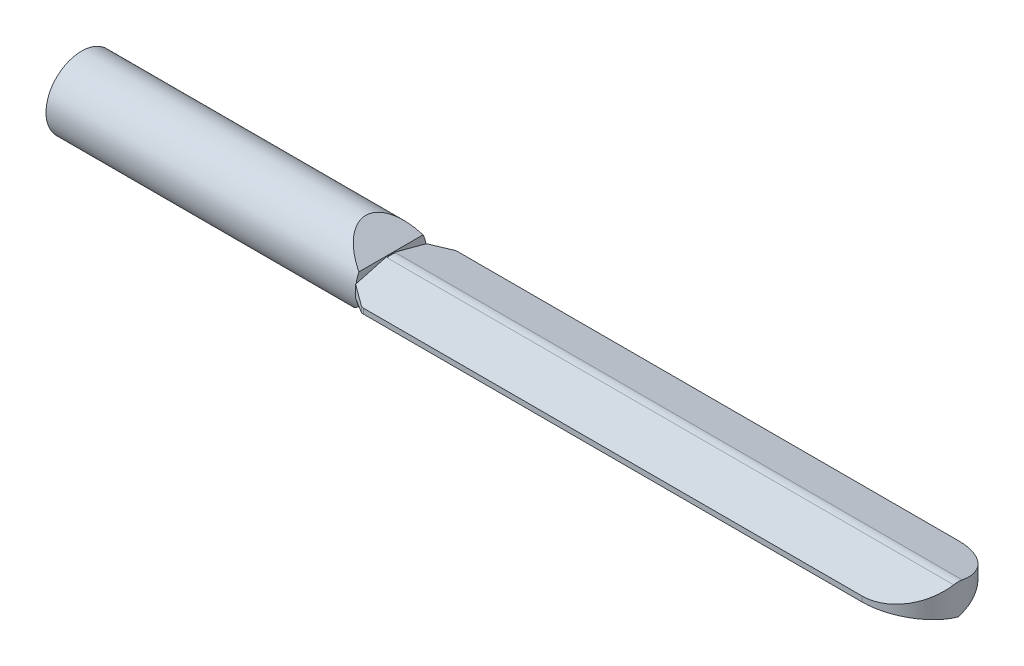
SolidWorks part; units mm, degrees
ref_plane "Front Plane" through (0, 0, 0) normal (0, 0, 1) x (1, 0, 0)
ref_plane "Top Plane" through (0, 0, 0) normal (0, 1, 0) x (1, 0, 0)
ref_plane "Right Plane" through (0, 0, 0) normal (1, 0, 0) x (0, 0, -1)
sketch "Sketch3" plane through (0, 0, 0) normal (0, 1, 0) x (1, 0, 0)
  line L0 (-55.9582, 0) -> (34.8662, 0)
  line L2 (34.8662, -17.3778) -> (-55.6338, -17.3778)
  line L5 (-55.9582, 0) -> (-59.1322, -2.1733)
  line L6 (-55.6338, -17.3778) -> (-59.1338, -14.9778)
  line L10 (-59.1322, -8.5778) -> (-59.1322, -2.1733)
  line L11 (-59.1338, -14.9778) -> (-59.1322, -8.5778)
  arc A0 (34.8662, 0) -> (34.8662, -17.3778) centre (34.8662, -8.6889) cw
extrude "Boss-Extrude2" add sketch "Sketch3" along normal blind 5.6 contours L10 L5 L0 A0 L2 L6 L11
chamfer "Chamfer2" distance 8.69 angle 15 1 edges at (-10.3838, 5.6, 17.3778) first distance on face at (-30.0813, 5.6, 8.6407)
chamfer "Chamfer3" distance 8.69 angle 15 1 edges at (-10.3838, 0, 17.3778) first distance on face at (-30.0813, 0, 8.6407)
chamfer "Chamfer4" distance 8.69 angle 15 1 edges at (-10.546, 5.6, 0) first distance on face at (-25.5224, 5.6, 4.3879)
chamfer "Chamfer5" distance 8.69 angle 15 1 edges at (-10.546, 0, 0) first distance on face at (-25.5224, 0, 4.3879)
fillet "Fillet1" radius 1 1 edges at (-55.6338, 2.8, 17.3778)
sketch "Sketch8" plane through (-59.1302, 0, -0.014) normal (-1, 0, -0.0002) x (-0.0002, 0, 1)
  line L0 (8.5919, 5.5699) -> (8.5919, 0.0301) construction
  circle A0 centre (8.5919, 2.8) radius 6.42
extrude "Boss-Extrude3" add sketch "Sketch8" along normal blind 58
fillet "Fillet2" radius 3 1 edges at (-7.7886, 5.5997, 8.6889)
sketch "Sketch16" plane through (0, 0, 0) normal (0, 0, 1) x (1, 0, 0)
  line L5 (-55.3238, 2.8) -> (-66.5609, 2.8) construction
  line L6 (-55.3238, 3.2715) -> (-55.3238, 2.3285) construction
  line L11 (-59.1322, 9.22) -> (-117.1322, 9.22) construction
  line L15 (-58.9437, 9.22) -> (-63.6937, 9.22)
  line L27 (-58.9437, 9.22) -> (-58.9437, 5.3917)
  line L28 (-58.9437, 5.3917) -> (-63.6937, 9.22)
  line L29 (-58.9437, -3.62) -> (-63.6937, -3.62)
  line L30 (-58.9437, 0.2083) -> (-63.6937, -3.62)
  line L31 (-58.9437, -3.62) -> (-58.9437, 0.2083)
  line L32 (43.5204, 5.3917) -> (-59.1325, 5.3917) construction
  point P4 (-58.9437, 5.3917)
extrude "Cut-Extrude12" cut sketch "Sketch16" along normal blind 16
sketch "Sketch19" plane through (0, 0, 0) normal (0, 1, 0) x (1, 0, 0)
  line L1 (-119.6827, 9.5404) -> (-115.1307, 9.5404)
  line L2 (-115.1307, 9.5404) -> (-115.1307, -21.4766)
  line L3 (-115.1307, -21.4766) -> (-119.6827, -21.4766)
  line L4 (-119.6827, -21.4766) -> (-119.6827, 9.5404)
  point P0 (-119.321, 9.5404)
extrude "Cut-Extrude13" cut sketch "Sketch19" along normal through all both and the other way through all
